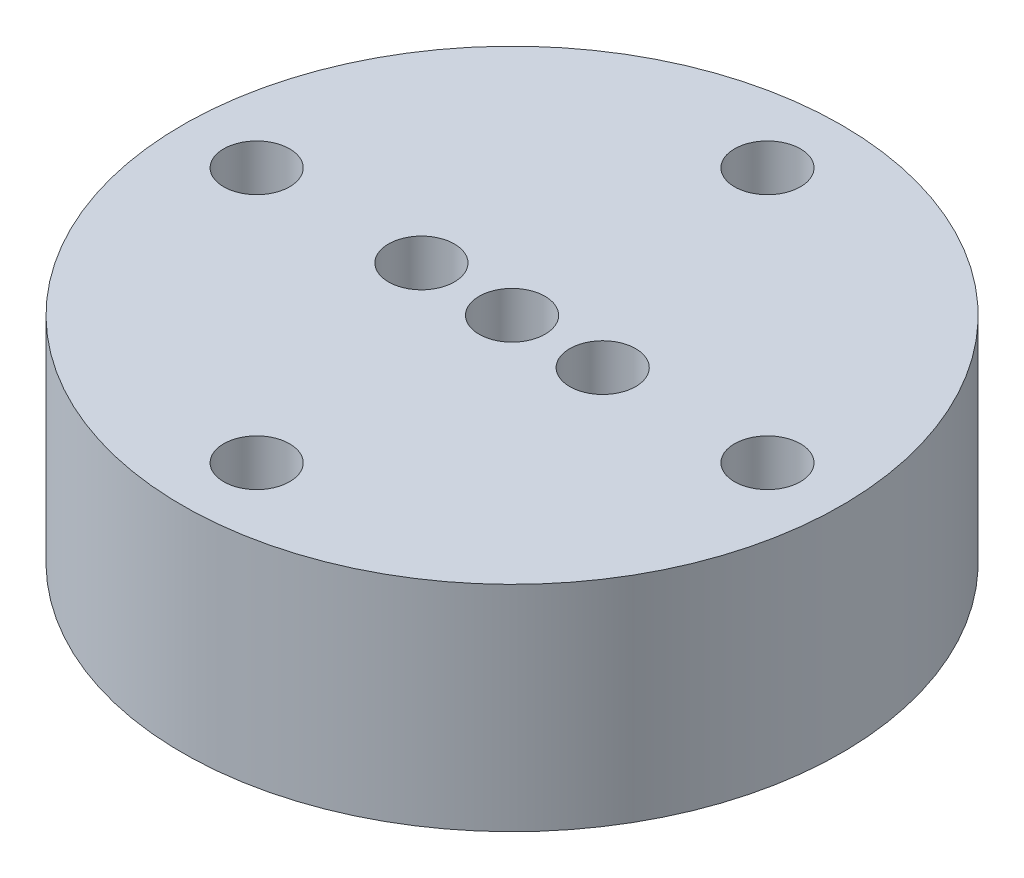
SolidWorks part; units mm, degrees
ref_plane "Front Plane" through (0, 0, 0) normal (0, 0, 1) x (1, 0, 0)
ref_plane "Top Plane" through (0, 0, 0) normal (0, 1, 0) x (1, 0, 0)
ref_plane "Right Plane" through (0, 0, 0) normal (1, 0, 0) x (0, 0, -1)
sketch "Sketch1" plane through (0, 0, 0) normal (0, 1, 0) x (1, 0, 0)
  circle A0 centre (0, 0) radius 15.5 construction
  circle A1 centre (0, 15.5) radius 2
  circle A2 centre (15.5, 0) radius 2
  circle A3 centre (0, -15.5) radius 2
  circle A4 centre (-15.5, 0) radius 2
  circle A5 centre (0, 0) radius 20
  circle A6 centre (0, 0) radius 4 construction
  point P14 (0, 0)
  dimension "D1" = 31
  dimension "D2" = 4
  dimension "D4" = 40
  dimension "D5" = 8
  dimension "D3" = 4
extrude "Boss-Extrude1" add sketch "Sketch1" along normal blind 13
sketch "Sketch2" plane through (0, 13, 0) normal (0, 1, 0) x (1, 0, 0)
  circle A0 centre (0, 0) radius 5.5 construction
  circle A1 centre (0, 0) radius 2
  circle A2 centre (5.5, 0) radius 2
  circle A3 centre (-5.5, 0) radius 2
  dimension "D1" = 11
  dimension "D2" = 4
  dimension "D3" = 4
  dimension "D4" = 4
extrude "Cut-Extrude1" cut sketch "Sketch2" against normal through all
